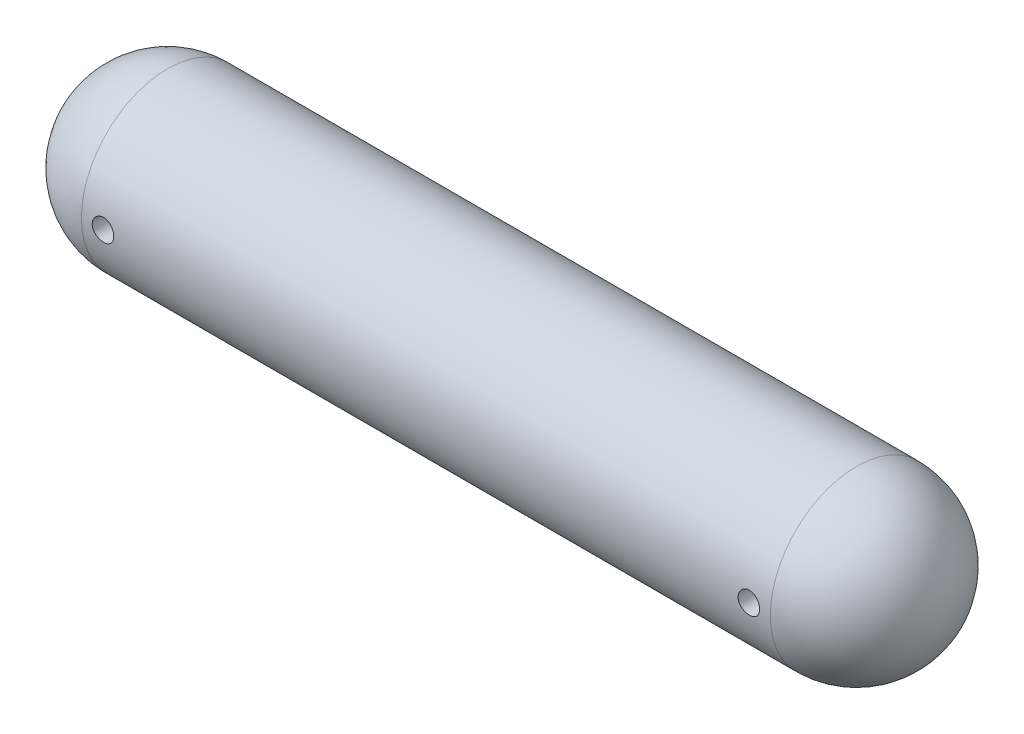
SolidWorks part; units mm, degrees
material "Aleación 2014"
ref_plane "Alzado" through (0, 0, 0) normal (0, 0, 1) x (1, 0, 0)
ref_plane "Planta" through (0, 0, 0) normal (0, 1, 0) x (1, 0, 0)
ref_plane "Vista lateral" through (0, 0, 0) normal (1, 0, 0) x (0, 0, -1)
sketch "Croquis3" plane through (0, 0, 0) normal (0, 1, 0) x (1, 0, 0)
  line L0 (-63.0853, 0) -> (72.028, 0) construction
  line L2 (-52.9193, 0) -> (-32.9193, 0) construction
  line L5 (147.0807, 0) -> (47.0807, 0) construction
  line L6 (-32.9193, 20) -> (107.0807, 20)
  line L8 (147.0807, 0) -> (127.0807, 0) construction
  line L11 (-52.9193, 0) -> (147.0807, 0)
  line L12 (127.0807, 20) -> (107.0807, 20)
  arc A4 (-32.9193, 20) -> (-52.9193, 0) centre (-32.9193, 0) ccw
  arc A8 (147.0807, 0) -> (127.0807, 20) centre (127.0807, 0) ccw
  dimension "D2" = 20
  dimension "D4" = 200
revolve "Revolución10" add sketch "Croquis3" angle 360 about L0
sketch "Croquis6" plane through (0, 0, 0) normal (0, 0, 1) x (1, 0, 0)
  line L0 (47.0807, 32.201) -> (47.0807, -35.8143) construction
  line L2 (-32.9193, 0) -> (-27.9193, 0) construction
  circle A3 centre (-27.9193, 0) radius 2.5
  circle A4 centre (122.0807, 0) radius 2.5
  dimension "D2" = 5
  dimension "D1" = 5
extrude "Cortar-Extruir1" cut sketch "Croquis6" against normal through all both and the other way through all
